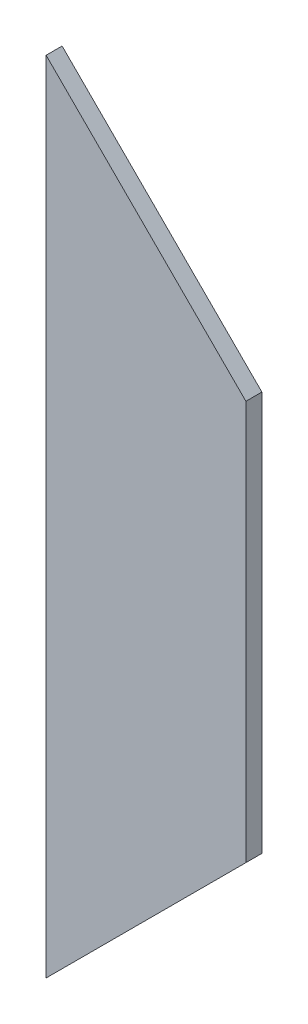
SolidWorks part; units mm, degrees
material "Сосна"
ref_plane "Спереди" through (0, 0, 0) normal (0, 0, 1) x (1, 0, 0)
ref_plane "Сверху" through (0, 0, 0) normal (0, 1, 0) x (1, 0, 0)
ref_plane "Справа" through (0, 0, 0) normal (1, 0, 0) x (0, 0, -1)
sketch "Эскиз1" plane through (0, 0, 0) normal (0, 0, 1) x (1, 0, 0)
  line L0 (0, 0) -> (0, 200)
  line L1 (0, 0) -> (50, 50)
  line L2 (50, 50) -> (50, 150)
  line L3 (50, 150) -> (0, 200)
  dimension "D1" = 200
  dimension "D2" = 50
  dimension "D3" = 45
  dimension "D4" = 45
extrude "Бобышка-Вытянуть1" add sketch "Эскиз1" along normal blind 4
sketch "Эскиз3" plane through (0, 0, 0) normal (-1, 0, 0) x (0, 0, 1)
  line L0 (2, 200) -> (2, -113.6649) construction
  line L1 (4, 200) -> (0, 200) construction
sketch "Эскиз4" plane through (50, 0, 0) normal (1, 0, 0) x (0, 0, -1)
  line L0 (-2, 150) -> (-2, -28.0184) construction
  line L1 (-4, 150) -> (0, 150) construction
